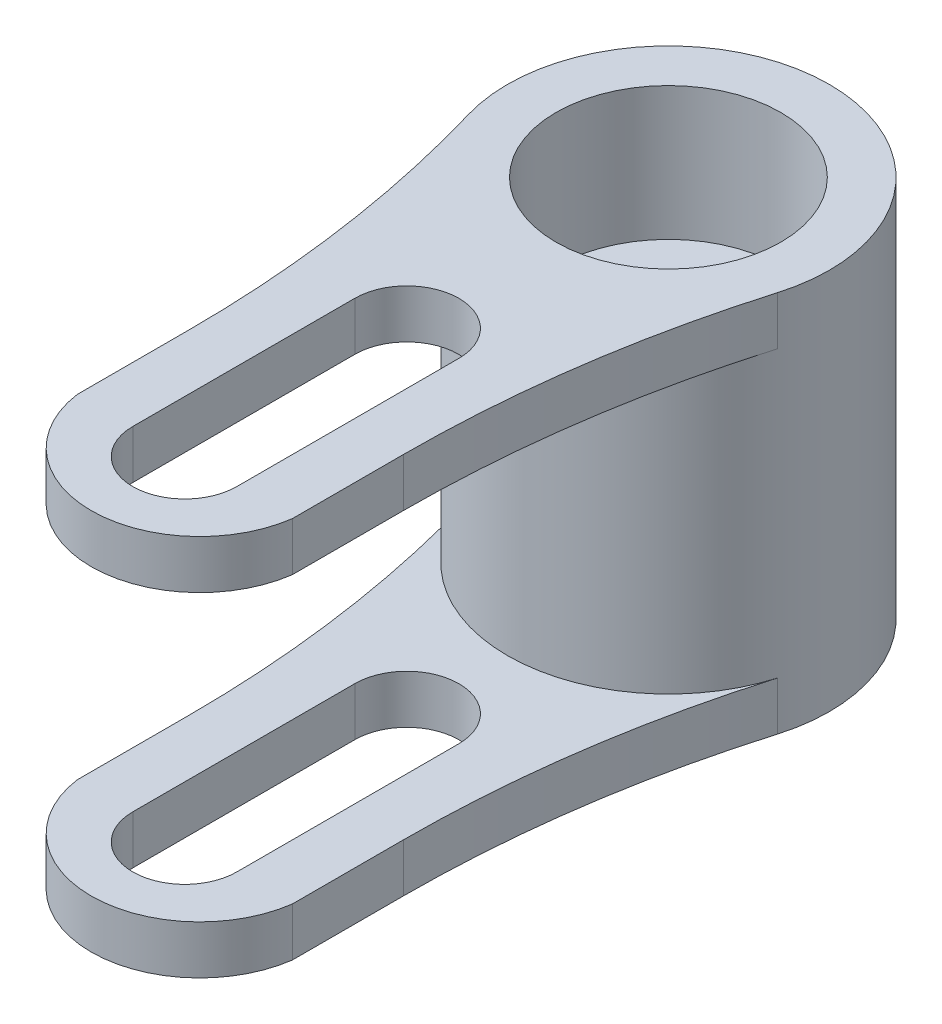
SolidWorks part; units mm, degrees
ref_plane "Front Plane" through (0, 0, 0) normal (0, 0, 1) x (1, 0, 0)
ref_plane "Top Plane" through (0, 0, 0) normal (0, 1, 0) x (1, 0, 0)
ref_plane "Right Plane" through (0, 0, 0) normal (1, 0, 0) x (0, 0, -1)
sketch "Sketch1" plane through (0, 0, 0) normal (0, 1, 0) x (1, 0, 0)
  line L0 (0, 5.8) -> (0, 4.05) construction
  line L1 (0, -9.425) -> (0, -17.425) construction
  line L2 (-3.875, -13.425) -> (-3.875, -17.425)
  line L3 (3.875, -17.425) -> (3.875, -13.425)
  line L4 (1.875, -9.425) -> (1.875, -17.425)
  line L5 (-1.875, -9.425) -> (-1.875, -17.425)
  line L6 (0, -7.55) -> (0, -5.8) construction
  line L7 (-3.875, -13.425) -> (3.875, -13.425) construction
  circle A0 centre (0, 0) radius 4.05
  circle A1 centre (0, 0) radius 5.8
  arc A2 (1.875, -9.425) -> (-1.875, -9.425) centre (0, -9.425) ccw
  arc A3 (-5.5663, -1.6298) -> (-3.875, -13.425) centre (-45.8506, -13.425) cw
  arc A4 (-3.875, -17.425) -> (3.875, -17.425) centre (0, -17.425) ccw
  arc A5 (3.875, -13.425) -> (5.5663, -1.6298) centre (45.8506, -13.425) cw
  arc A6 (-1.875, -17.425) -> (1.875, -17.425) centre (0, -17.425) ccw
  point P6 (0, -13.425)
  dimension "D1" = 8.1
  dimension "D2" = 1.75
  dimension "D3" = 3.75
  dimension "D4" = 2
  dimension "D5" = 8
  dimension "D6" = 1.75
extrude "Boss-Extrude1" add sketch "Sketch1" along normal mid plane 13.775 contours L3 A5 A1 A3 L2 A4 A6 L5 A2 L4 | A0 | A1 A0 region at (-4.0762, 0, 7.435) region at (-0.8, 0, -5.5789) region at (0, 0, 0)
ref_plane "Plane1" through (0, -5.1375, 0) normal (0, -1, 0) x (-1, 0, 0)
ref_plane "Plane2" through (0, 5.1375, 0) normal (0, 1, 0) x (1, 0, 0)
extrude "Cut-Extrude1" cut sketch "Sketch1<4>" along normal up to surface (10.275 mm away) from surface contours L3 A5 A1 A3 L2 A4 A6 L5 A2 L4 region at (-4.0762, 0, 7.435) up to plane "Plane2" starting at plane "Plane1"
sketch "Sketch1<4>" plane through (0, 0, 0) normal (0, 1, 0) x (1, 0, 0) same geometry as "Sketch1"
extrude "Cut-Extrude2" cut sketch "Sketch1<5>" against normal blind 4.8 from surface contours A0 region at (0, 0, 0) starting at face at (0, 6.8875, 13.425)
sketch "Sketch1<5>" plane through (0, 0, 0) normal (0, 1, 0) x (1, 0, 0) same geometry as "Sketch1"
sketch "Sketch4" plane through (0, -6.8875, 0) normal (0, -1, 0) x (1, 0, 0)
  line L2 (0, 20.8) -> (0, 21.3) construction
  line L4 (0, 20.8) -> (0, 19.3) construction
  arc A0 (3.875, 17.425) -> (-3.875, 17.425) centre (0, 17.425) ccw construction
  arc A1 (1.875, 17.425) -> (-1.875, 17.425) centre (0, 17.425) ccw construction
  arc A3 (-3.875, 17.425) -> (3.875, 17.425) centre (0, 16.888) cw
  arc A4 (3.875, 17.425) -> (-3.875, 17.425) centre (0, 17.425) ccw
  point P12 (-3.875, 17.425)
  dimension "D1" = 0.5
extrude "Cut-Extrude3" cut sketch "Sketch4" against normal through all
equation "\"D1@Boss-Extrude1\"=9.525mm+1.75mm+1.75mm+.75mm"
